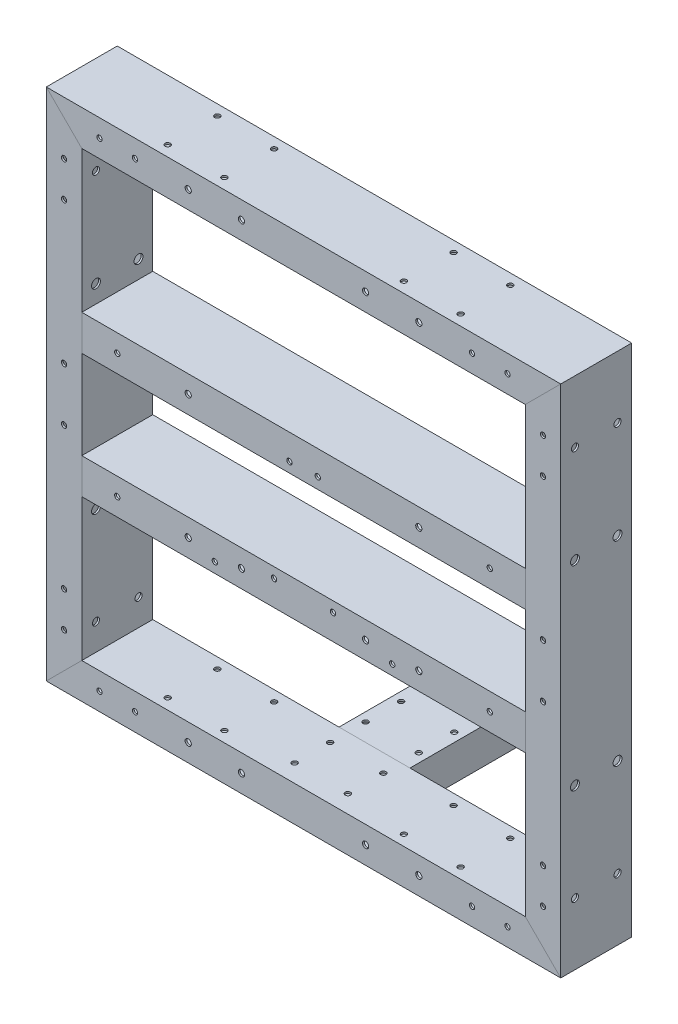
SolidWorks part; units mm, degrees
material "7050-T7651"
ref_plane "前视基准面" through (0, 0, 0) normal (0, 0, 1) x (1, 0, 0)
ref_plane "上视基准面" through (0, 0, 0) normal (0, 1, 0) x (1, 0, 0)
ref_plane "右视基准面" through (0, 0, 0) normal (1, 0, 0) x (0, 0, -1)
sketch "草图1" plane through (0, 0, 0) normal (0, 0, 1) x (1, 0, 0)
  line L0 (0, 0) -> (270, 0)
  line L1 (270, 0) -> (270, -270)
  line L2 (270, -270) -> (0, -270)
  line L3 (0, -270) -> (0, 0)
  line L4 (0, -270) -> (0, -170) construction
  line L5 (0, -170) -> (270, -170)
  line L6 (0, 0) -> (0, -100) construction
  line L7 (0, -100) -> (270, -100)
  dimension "D1" = 270
  dimension "D2" = 270
  dimension "D3" = 100
  dimension "D4" = 100
other "20x40x1 LVGUAN20X40(1)" corner treatment miter
ref_plane "基准面1" through (0, -270, 0) normal (0, 1, 0) x (0, 0, 1)
sketch "草图11" plane through (0, -270, 0) normal (0, 1, 0) x (0, 0, 1)
  line L1 (-20, 10) -> (20, 10)
  line L2 (-20, 10) -> (-20, -10)
  line L3 (-20, -10) -> (20, -10)
  line L4 (20, 10) -> (20, -10)
  line L5 (-20, 10) -> (20, -10) construction
  line L6 (-20, -10) -> (20, 10) construction
  line L7 (-19, 9) -> (19, 9)
  line L8 (-19, 9) -> (-19, -9)
  line L9 (-19, -9) -> (19, -9)
  line L10 (19, 9) -> (19, -9)
  line L11 (-19, 9) -> (19, -9) construction
  line L12 (-19, -9) -> (19, 9) construction
  point P0 (0, 0)
  point P5 (0, 0)
  point P11 (0, 0)
  dimension "D1" = 20
  dimension "D2" = 40
  dimension "D3" = 18
  dimension "D4" = 38
sketch "草图12" plane through (-10, 0, 0) normal (-1, 0, 0) x (0, 0, 1)
  line L0 (0, 10) -> (0, -110) construction
  line L1 (20, 10) -> (-20, 10) construction
  line L2 (0, -280) -> (0, -160) construction
  line L3 (20, -280) -> (-20, -280) construction
  line L4 (0, -110) -> (0, -160) construction
  line L6 (-12, -75) -> (12, -75) construction
  line L7 (-12, -75) -> (-12, -25) construction
  line L8 (-12, -25) -> (12, -25) construction
  line L9 (12, -75) -> (12, -25) construction
  line L10 (-12, -75) -> (12, -25) construction
  line L11 (-12, -25) -> (12, -75) construction
  line L12 (-12, -160) -> (12, -160) construction
  line L13 (-12, -160) -> (-12, -110) construction
  line L14 (-12, -110) -> (12, -110) construction
  line L15 (12, -160) -> (12, -110) construction
  line L16 (-12, -160) -> (12, -110) construction
  line L17 (-12, -110) -> (12, -160) construction
  line L18 (-12, -245) -> (12, -245) construction
  line L19 (-12, -245) -> (-12, -195) construction
  line L20 (-12, -195) -> (12, -195) construction
  line L21 (12, -245) -> (12, -195) construction
  line L22 (-12, -245) -> (12, -195) construction
  line L23 (-12, -195) -> (12, -245) construction
  circle A0 centre (-12, -25) radius 2
  circle A1 centre (12, -25) radius 2
  circle A10 centre (-12, -245) radius 2
  circle A11 centre (12, -245) radius 2
  point P9 (0, -50)
  point P18 (0, -135)
  point P27 (0, -220)
  dimension "D5" = 4
  dimension "D6" = 4
  dimension "D19" = 4
  dimension "D20" = 4
  dimension "D1" = 120
  dimension "D2" = 120
  dimension "D3" = 50
  dimension "D4" = 24
  dimension "D9" = 50
  dimension "D10" = 24
  dimension "D15" = 50
  dimension "D16" = 24
extrude "切除-拉伸1" cut sketch "草图12" against normal blind 318
sketch "草图14" plane through (0, 0, 20) normal (0, 0, 1) x (1, 0, 0)
  line L0 (135, -160) -> (135, -180) construction
  line L1 (260, -160) -> (10, -160) construction
  line L2 (260, -180) -> (10, -180) construction
  line L3 (135, -170) -> (185, -170) construction
  line L4 (185, -170) -> (85, -170) construction
  line L5 (85, -170) -> (85, -174.25) construction
  line L6 (85, -174.25) -> (185, -174.25) construction
  line L7 (85, -174.25) -> (85, -165.75) construction
  line L8 (85, -165.75) -> (135, -165.75) construction
  line L9 (135, -165.75) -> (118.4, -165.75) construction
  line L10 (118.4, -165.75) -> (151.6, -165.75) construction
  circle A2 centre (85, -174.25) radius 1.5
  circle A3 centre (185, -174.25) radius 1.5
  circle A4 centre (118.4, -165.75) radius 1.5
  circle A5 centre (151.6, -165.75) radius 1.5
  dimension "D3" = 8.5
  dimension "D4" = 16.6
  dimension "D6" = 3
  dimension "D7" = 3
  dimension "D9" = 3
  dimension "D10" = 3
  dimension "D1" = 50
  dimension "D2" = 100
  dimension "D5" = 4.25
  dimension "D8" = 33.2
extrude "切除-拉伸3" cut sketch "草图14" against normal blind 318
sketch "草图16" plane through (0, 0, 20) normal (0, 0, 1) x (1, 0, 0)
  circle A2 centre (127.0469, -104.3472) radius 1.5
  circle A3 centre (143.0368, -103.7788) radius 1.5
extrude "切除-拉伸5" cut sketch "草图16" against normal blind 50
sketch "草图17" plane through (280, 0, 0) normal (1, 0, 0) x (0, 0, -1)
  line L0 (-20, -135) -> (20, -135) construction
  line L1 (-20, -280) -> (-20, 10) construction
  line L2 (20, -280) -> (20, 10) construction
  line L4 (-12, -190) -> (12, -190) construction
  line L5 (-12, -190) -> (-12, -80) construction
  line L6 (-12, -80) -> (12, -80) construction
  line L7 (12, -190) -> (12, -80) construction
  line L8 (-12, -190) -> (12, -80) construction
  line L9 (-12, -80) -> (12, -190) construction
  circle A0 centre (-12, -80) radius 2.5
  circle A1 centre (12, -80) radius 2.5
  circle A2 centre (-12, -190) radius 2.5
  circle A3 centre (12, -190) radius 2.5
  point P6 (0, -135)
  dimension "D3" = 5
  dimension "D4" = 5
  dimension "D5" = 5
  dimension "D6" = 5
  dimension "D1" = 110
  dimension "D2" = 24
sketch3d "3D草图2"
  line L0 (135, -280, -20) -> (135, -270, -20) construction
  line L1 (-10, -280, -20) -> (280, -280, -20) construction
  line L2 (135, -270, -20) -> (135, -270, -110)
  dimension "D1" = 10
  dimension "D2" = 90
sketch "草图113" plane through (0, 10, 0) normal (0, 1, 0) x (1, 0, 0)
  circle A8 centre (217.6, 14) radius 1.5
  circle A9 centre (217.6, -14) radius 1.5
  circle A10 centre (185.6, -14) radius 1.5
  circle A11 centre (185.6, 14) radius 1.5
  circle A12 centre (84.4, -14) radius 1.5
  circle A13 centre (52.4, -14) radius 1.5
  circle A14 centre (52.4, 14) radius 1.5
  circle A15 centre (84.4, 14) radius 1.5
extrude "切除-拉伸7" cut sketch "草图113" against normal blind 20
sketch "草图114" plane through (0, -280, 0) normal (0, -1, 0) x (1, 0, 0)
  circle A4 centre (185.6, -14) radius 1.5
  circle A5 centre (217.6, -14) radius 1.5
  circle A6 centre (217.6, 14) radius 1.5
  circle A7 centre (185.6, 14) radius 1.5
  circle A12 centre (52.4, 14) radius 1.5
  circle A13 centre (52.4, -14) radius 1.5
  circle A14 centre (84.4, -14) radius 1.5
  circle A15 centre (84.4, 14) radius 1.5
extrude "切除-拉伸8" cut sketch "草图114" against normal blind 29
extrude "切除-拉伸12" cut sketch "草图17" against normal blind 357
other "20x20x1 LVGUAN20X20(2)" corner treatment miter
ref_plane "基准面2" through (135, -270, -20) normal (0, 0, -1) x (1, 0, 0)
sketch "草图119" plane through (135, -270, -20) normal (0, 0, -1) x (1, 0, 0)
  line L1 (10, -10) -> (-10, -10)
  line L2 (10, -10) -> (10, 10)
  line L3 (10, 10) -> (-10, 10)
  line L4 (-10, -10) -> (-10, 10)
  line L5 (10, -10) -> (-10, 10) construction
  line L6 (10, 10) -> (-10, -10) construction
  line L7 (9, -9) -> (-9, -9)
  line L8 (9, -9) -> (9, 9)
  line L9 (9, 9) -> (-9, 9)
  line L10 (-9, -9) -> (-9, 9)
  line L11 (9, -9) -> (-9, 9) construction
  line L12 (9, 9) -> (-9, -9) construction
  point P0 (0, 0)
  point P5 (0, 0)
  point P11 (0, 0)
  dimension "D1" = 20
  dimension "D2" = 18
sketch "草图120" plane through (0, -260, 0) normal (0, 1, 0) x (1, 0, 0)
  line L0 (135, 110) -> (135, 95) construction
  line L1 (125, 110) -> (145, 110) construction
  line L7 (129, 85) -> (141, 85) construction
  line L8 (129, 85) -> (129, 105) construction
  line L9 (129, 105) -> (141, 105) construction
  line L10 (141, 85) -> (141, 105) construction
  line L11 (129, 85) -> (141, 105) construction
  line L12 (129, 105) -> (141, 85) construction
  circle A4 centre (129, 105) radius 1.5
  circle A5 centre (141, 105) radius 1.5
  circle A6 centre (141, 85) radius 1.5
  circle A7 centre (129, 85) radius 1.5
  dimension "D3" = 12
  dimension "D4" = 3
  dimension "D5" = 3
  dimension "D6" = 3
  dimension "D7" = 3
  dimension "D1" = 15
  dimension "D2" = 20
extrude "切除-拉伸13" cut sketch "草图120" against normal blind 30
sketch "草图121" plane through (0, 0, 20) normal (0, 0, 1) x (1, 0, 0)
  circle A8 centre (170, -270) radius 1.75
  circle A9 centre (100, -270) radius 1.75
  circle A10 centre (100, -170) radius 1.75
  circle A11 centre (170, -170) radius 1.75
  circle A12 centre (200, -170) radius 1.75
  circle A13 centre (70, -170) radius 1.75
  circle A14 centre (70, -270) radius 1.75
  circle A15 centre (200, -270) radius 1.75
extrude "切除-拉伸14" cut sketch "草图121" against normal blind 100
sketch "草图122" plane through (0, 0, -20) normal (0, 0, -1) x (-1, 0, 0)
  circle A4 centre (-200, -100) radius 1.75
  circle A5 centre (-70, -100) radius 1.75
  circle A6 centre (-70, 0) radius 1.75
  circle A7 centre (-200, 0) radius 1.75
extrude "切除-拉伸15" cut sketch "草图122" against normal blind 40
sketch "草图123" plane through (0, 0, -20) normal (0, 0, -1) x (-1, 0, 0)
  circle A4 centre (-240, -100) radius 1.5
  circle A5 centre (-240, -170) radius 1.5
  circle A6 centre (-30, -100) radius 1.5
  circle A7 centre (-30, -170) radius 1.5
extrude "切除-拉伸16" cut sketch "草图123" against normal blind 40
sketch "草图125" plane through (0, 0, -20) normal (0, 0, -1) x (-1, 0, 0)
  line L0 (0, -270) -> (-20, -270) construction
  line L1 (-20, -270) -> (-40, -270)
  line L2 (10, -280) -> (-10, -260) construction
  line L3 (-135, -260) -> (-135, -286.5178) construction
  line L4 (-125, -260) -> (-145, -260) construction
  line L5 (-10, -135) -> (-46.6883, -135) construction
  line L6 (-10, -10) -> (-10, -260) construction
  line L7 (0, -270) -> (0, -250) construction
  line L8 (0, -250) -> (0, -230)
  line L9 (-270, -270) -> (-270, -250) construction
  line L10 (-280, -280) -> (-260, -260) construction
  line L11 (-270, -270) -> (-250, -270) construction
  line L12 (-270, -250) -> (-270, -230)
  line L13 (-250, -270) -> (-230, -270)
  line L14 (0, 0) -> (0, -20) construction
  line L15 (10, 10) -> (-10, -10) construction
  line L16 (0, 0) -> (-20, 0) construction
  line L17 (0, -20) -> (0, -40)
  line L18 (-20, 0) -> (-40, 0)
  line L19 (-270, 0) -> (-250, 0) construction
  line L20 (-280, 10) -> (-260, -10) construction
  line L21 (-270, 0) -> (-270, -20) construction
  line L22 (-250, 0) -> (-230, 0)
  line L23 (-270, -20) -> (-270, -40)
  circle A0 centre (-40, -270) radius 1.5
  circle A1 centre (-20, -270) radius 1.5
  circle A2 centre (0, -250) radius 1.5
  circle A3 centre (0, -230) radius 1.5
  circle A4 centre (-270, -230) radius 1.5
  circle A5 centre (-270, -250) radius 1.5
  circle A6 centre (-250, -270) radius 1.5
  circle A7 centre (-230, -270) radius 1.5
  circle A8 centre (0, -40) radius 1.5
  circle A9 centre (0, -20) radius 1.5
  circle A10 centre (-20, 0) radius 1.5
  circle A11 centre (-40, 0) radius 1.5
  circle A12 centre (-230, 0) radius 1.5
  circle A13 centre (-250, 0) radius 1.5
  circle A14 centre (-270, -20) radius 1.5
  circle A15 centre (-270, -40) radius 1.5
  dimension "D3" = 3
  dimension "D4" = 3
  dimension "D1" = 20
  dimension "D2" = 20
extrude "切除-拉伸18" cut sketch "草图125" against normal blind 40
sketch "草图126" plane through (0, 0, -20) normal (0, 0, -1) x (-1, 0, 0)
  line L0 (-10, -135) -> (10, -135) construction
  line L1 (-10, -10) -> (-10, -260) construction
  line L2 (10, 10) -> (10, -280) construction
  line L3 (0, -135) -> (0, -120) construction
  line L4 (-135, -90) -> (-135, -180) construction
  line L5 (-260, -90) -> (-10, -90) construction
  line L6 (-260, -180) -> (-10, -180) construction
  line L7 (-270, -135) -> (-270, -120) construction
  line L8 (-260, -135) -> (-280, -135) construction
  circle A0 centre (0, -120) radius 1.5
  circle A1 centre (0, -150) radius 1.5
  circle A2 centre (-270, -150) radius 1.5
  circle A3 centre (-270, -120) radius 1.5
  dimension "D2" = 3
  dimension "D1" = 15
extrude "切除-拉伸19" cut sketch "草图126" against normal blind 40
delete or keep bodies "实体-删除/保留 1" type keep bodies bodies 155 154 153 156 138 145 146
sketch "草图130" plane through (0, 0, -20) normal (0, 0, -1) x (-1, 0, 0)
  line L0 (-125, -260) -> (-145, -260) construction
  line L1 (-145, -260) -> (-145, -280) construction
  line L2 (-125, -280) -> (-125, -260) construction
  line L3 (-145, -280) -> (-125, -280) construction
  line L4 (-144, -279) -> (-126, -279) construction
  line L5 (-126, -279) -> (-126, -261) construction
  line L6 (-126, -261) -> (-144, -261) construction
  line L7 (-144, -261) -> (-144, -279) construction
  line L8 (-125, -260) -> (-145, -260)
  line L9 (-145, -260) -> (-145, -280)
  line L10 (-125, -280) -> (-125, -260)
  line L11 (-145, -280) -> (-125, -280)
  line L12 (-144, -279) -> (-126, -279)
  line L13 (-126, -279) -> (-126, -261)
  line L14 (-126, -261) -> (-144, -261)
  line L15 (-144, -261) -> (-144, -279)
extrude "切除-拉伸21" cut sketch "草图130" along normal blind 100
other "20x40x1 LVGUAN20X40(3)" corner treatment miter
ref_plane "基准面3" through (135, -270, -20) normal (0, 0, -1) x (1, 0, 0)
sketch "草图131" plane through (135, -270, -20) normal (0, 0, -1) x (1, 0, 0)
  line L1 (-20, 10) -> (20, 10)
  line L2 (-20, 10) -> (-20, -10)
  line L3 (-20, -10) -> (20, -10)
  line L4 (20, 10) -> (20, -10)
  line L5 (-20, 10) -> (20, -10) construction
  line L6 (-20, -10) -> (20, 10) construction
  line L7 (-19, 9) -> (19, 9)
  line L8 (-19, 9) -> (-19, -9)
  line L9 (-19, -9) -> (19, -9)
  line L10 (19, 9) -> (19, -9)
  line L11 (-19, 9) -> (19, -9) construction
  line L12 (-19, -9) -> (19, 9) construction
  point P0 (0, 0)
  point P5 (0, 0)
  point P11 (0, 0)
  dimension "D1" = 20
  dimension "D2" = 40
  dimension "D3" = 18
  dimension "D4" = 38
sketch "草图132" plane through (0, -280, 0) normal (0, -1, 0) x (1, 0, 0)
  line L0 (135, -110) -> (135, -95) construction
  line L1 (155, -110) -> (115, -110) construction
  line L3 (119, -87.5) -> (151, -87.5) construction
  line L4 (119, -87.5) -> (119, -102.5) construction
  line L5 (119, -102.5) -> (151, -102.5) construction
  line L6 (151, -87.5) -> (151, -102.5) construction
  line L7 (119, -87.5) -> (151, -102.5) construction
  line L8 (119, -102.5) -> (151, -87.5) construction
  circle A0 centre (119, -87.5) radius 1.5
  circle A1 centre (151, -87.5) radius 1.5
  circle A2 centre (151, -102.5) radius 1.5
  circle A3 centre (119, -102.5) radius 1.5
  dimension "D4" = 3
  dimension "D5" = 3
  dimension "D6" = 3
  dimension "D7" = 3
  dimension "D1" = 15
  dimension "D2" = 15
  dimension "D3" = 32
extrude "切除-拉伸22" cut sketch "草图132" against normal blind 100
sketch "草图133" plane through (0, -280, 0) normal (0, -1, 0) x (1, 0, 0)
  line L0 (135, 20) -> (135, -60) construction
  line L1 (-10, 20) -> (280, 20) construction
  line L2 (135, -60) -> (135, -40) construction
  line L3 (135, 0) -> (169.457, 0) construction
  line L4 (120, -50) -> (150, -50) construction
  line L5 (120, -50) -> (120, -30) construction
  line L6 (120, -30) -> (150, -30) construction
  line L7 (150, -50) -> (150, -30) construction
  line L8 (120, -50) -> (150, -30) construction
  line L9 (120, -30) -> (150, -50) construction
  line L10 (155, -20) -> (115, -20) construction
  circle A0 centre (120, -30) radius 1.5
  circle A1 centre (150, -30) radius 1.5
  circle A2 centre (150, -50) radius 1.5
  circle A3 centre (120, -50) radius 1.5
  circle A4 centre (120, 10) radius 1.5
  circle A5 centre (150, 10) radius 1.5
  circle A6 centre (150, -10) radius 1.5
  circle A7 centre (120, -10) radius 1.5
  dimension "D5" = 3
  dimension "D6" = 3
  dimension "D7" = 3
  dimension "D8" = 3
  dimension "D1" = 80
  dimension "D2" = 20
  dimension "D3" = 20
  dimension "D4" = 30
extrude "切除-拉伸23" cut sketch "草图133" against normal blind 35
sketch "草图134" plane through (0, 0, 20) normal (0, 0, 1) x (1, 0, 0)
  line L0 (10, -135) -> (260, -135) construction
  line L1 (10, -10) -> (10, -260) construction
  line L2 (260, -260) -> (260, -10) construction
  circle A0 centre (170, -270) radius 1.75 construction
  circle A1 centre (100, -270) radius 1.75 construction
  circle A2 centre (170, -270) radius 1.75
  circle A3 centre (100, -270) radius 1.75
  circle A4 centre (100, 0) radius 1.75
  circle A5 centre (170, 0) radius 1.75
extrude "切除-拉伸24" cut sketch "草图134" against normal blind 82
